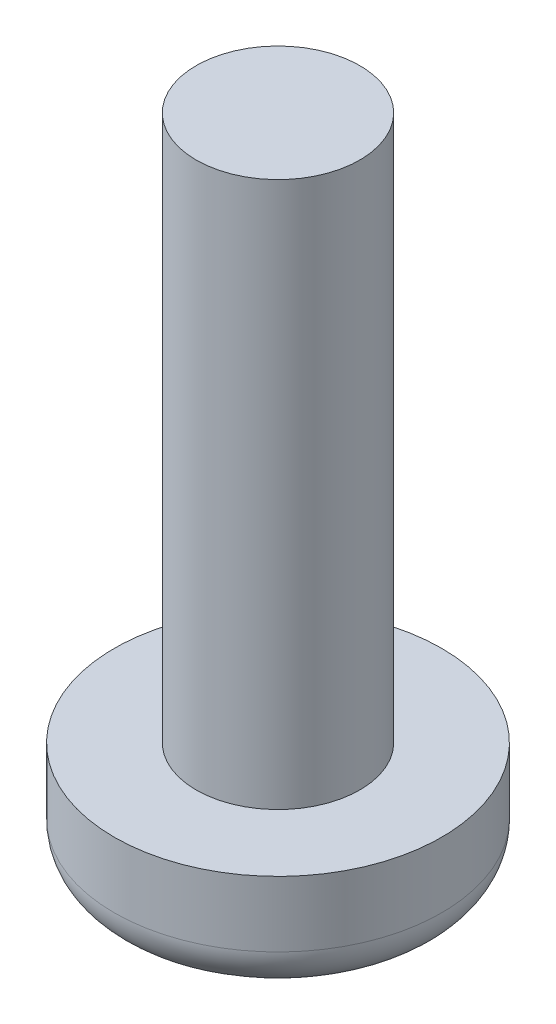
SolidWorks part; units mm, degrees
ref_plane "Plano frontal" through (0, 0, 0) normal (0, 0, 1) x (1, 0, 0)
ref_plane "Plano superior" through (0, 0, 0) normal (0, 1, 0) x (1, 0, 0)
ref_plane "Plano direito" through (0, 0, 0) normal (1, 0, 0) x (0, 0, -1)
sketch "Esboço1" plane through (0, 0, 0) normal (0, 1, 0) x (1, 0, 0)
  circle A0 centre (0, 0) radius 1.5
  circle A1 centre (0, 0) radius 3
  dimension "D1" = 3
  dimension "D2" = 6
extrude "Ressalto-extrusão1" add sketch "Esboço1" along normal blind 10 contours A0 region at (0, 0, 0)
extrude "Ressalto-extrusão2" add sketch "Esboço1<3>" against normal blind 2 separate body contours A1 A0 | A0 region at (0, 0, 0) region at (-2.9151, 0, 0)
sketch "Esboço1<3>" plane through (0, 0, 0) normal (0, 1, 0) x (1, 0, 0) same geometry as "Esboço1"
fillet "Filete1" radius 0.8 1 edges at (0, -2, 3)
